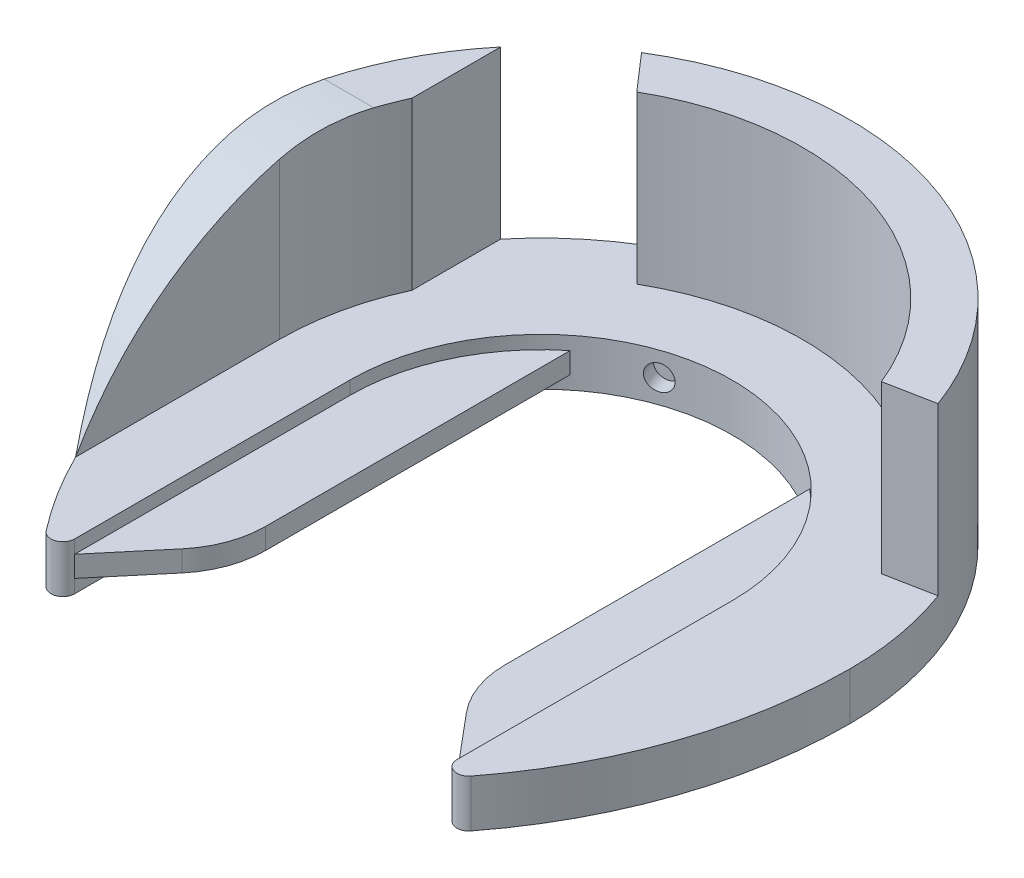
SolidWorks part; units mm, degrees
ref_plane "Front Plane" through (0, 0, 0) normal (0, 0, 1) x (1, 0, 0)
ref_plane "Top Plane" through (0, 0, 0) normal (0, 1, 0) x (1, 0, 0)
ref_plane "Right Plane" through (0, 0, 0) normal (1, 0, 0) x (0, 0, -1)
sketch "Sketch1" plane through (0, 0, 0) normal (0, 1, 0) x (1, 0, 0)
  line L3 (-40.2, 0) -> (-40.2, -57.8763)
  line L4 (40.2, 0) -> (40.2, -57.8763)
  line L5 (-25.2, -32.7206) -> (-25.2, 31.3209)
  line L6 (0, -55) -> (0, 55) construction
  line L7 (25.2, -32.7206) -> (25.2, 31.3209)
  line L8 (-40.2, -57.8763) -> (-29.8791, -45.5763)
  line L9 (40.2, -57.8763) -> (29.8791, -45.5763)
  line L10 (-55, 0) -> (-55, -42.8923)
  line L11 (55, 0) -> (55, -42.8923)
  arc A0 (65, 0) -> (-65, 0) centre (0, 0) ccw
  arc A1 (-65, 0) -> (65, 0) centre (0, 0) ccw construction
  arc A2 (40.2, 0) -> (-40.2, 0) centre (0, 0) ccw
  arc A3 (-65, 0) -> (-44.6761, -59.4076) centre (31.9875, 0) ccw
  arc A4 (65, 0) -> (44.6761, -59.4076) centre (-31.9875, 0) cw
  arc A5 (40.2, -57.8763) -> (44.6761, -59.4076) centre (42.7, -57.8763) ccw
  arc A6 (-40.2, -57.8763) -> (-44.6761, -59.4076) centre (-42.7, -57.8763) cw
  arc A8 (25.2, -32.7206) -> (29.8791, -45.5763) centre (45.2, -32.7206) ccw
  arc A9 (-25.2, -32.7206) -> (-29.8791, -45.5763) centre (-45.2, -32.7206) cw
  circle A10 centre (0, 0) radius 40.2 construction
  arc A11 (55, 0) -> (-55, 0) centre (0, 0) ccw
  point P9 (25.2, -40)
  point P19 (-25.2, -40)
  dimension "D1" = 130
  dimension "D2" = 80.4
  dimension "D4" = 2.5
  dimension "D6" = 40
  dimension "D7" = 20
  dimension "D8" = 80.4
  dimension "D9" = 110
  dimension "D3" = 50.4
  dimension "D5" = 40
extrude "Boss-Extrude1" add sketch "Sketch1" along normal blind 10 contours L11 A11 L10 A3 A6 L3 A2 L4 A5 A4 region at (-41.7941, 0, 28.9382)
extrude "Boss-Extrude2" add sketch "Sketch1<5>" along normal blind 4.4 from offset 2.8 contours A9 L5 A2 L3 L8 | L7 A8 L9 L4 A2 region at (-32.623, 0, 13.2342) region at (32.623, 0, 13.2342)
sketch "Sketch1<5>" plane through (0, 0, 0) normal (0, 1, 0) x (1, 0, 0) same geometry as "Sketch1"
extrude "Boss-Extrude3" add sketch "Sketch1<6>" along normal blind 45 contours A11 L11 A4 A0 A3 L10 region at (-60.8216, 0, 21.6377)
sketch "Sketch1<6>" plane through (0, 0, 0) normal (0, 1, 0) x (1, 0, 0) same geometry as "Sketch1"
sketch "Sketch2" plane through (0, 0, 0) normal (1, 0, 0) x (0, 0, -1)
  line L0 (-42.8923, 10) -> (-42.8923, 45)
  line L1 (-42.8923, 45) -> (17.1077, 45)
  arc A0 (-42.8923, 10) -> (17.1077, 45) centre (17.1077, -23.9286) cw
  dimension "D1" = 60
extrude "Cut-Extrude1" cut sketch "Sketch2" against normal through all both and the other way through all
sketch "Sketch3" plane through (0, 45, 0) normal (0, 1, 0) x (1, 0, 0)
  line L0 (-50.0082, 41.5232) -> (-43.344, 33.857) construction
  line L1 (-34.1593, 55.3005) -> (-27.4951, 47.6342)
  line L2 (0, 0) -> (0, 65) construction
  line L3 (0, 0) -> (-42.6438, 49.0561) construction
  line L4 (-50.0082, 41.5232) -> (-50.0082, 22.8949)
  line L7 (60.9643, 22.5468) -> (50.993, 20.6086)
  line L8 (0, 0) -> (63.8058, 12.4026) construction
  line L9 (0, 0) -> (-27.4951, 47.6342) construction
  line L10 (0, 0) -> (55, -0.0056) construction
  line L11 (60.9643, 22.5468) -> (44.8317, 31.8609) [skipped]
  line L12 (55, -0.0056) -> (55, -42.8923)
  line L13 (64.9713, 1.9326) -> (55, -0.0056) [skipped]
  arc A0 (62.7083, 17.1077) -> (-62.7083, 17.1077) centre (0, 0) ccw construction
  arc A1 (52.2717, 17.1077) -> (-52.2717, 17.1077) centre (0, 0) ccw construction
  arc A2 (55, 0) -> (-55, 0) centre (0, 0) ccw construction
  arc A3 (-50.0082, 41.5232) -> (-34.1593, 55.3005) centre (0, 0) cw
  arc A4 (-27.4951, 47.6342) -> (-43.344, 33.857) centre (0, 0) ccw
  arc A5 (-43.344, 33.857) -> (-50.0082, 22.8949) centre (0, 0) ccw
  arc A7 (55, -0.0056) -> (50.993, 20.6086) centre (0, 0) ccw
  arc A9 (50.993, 20.6086) -> (44.8317, 31.8609) centre (0, 0) ccw [skipped]
  arc A10 (60.9643, 22.5468) -> (65, 0) centre (0, 0) cw
  arc A11 (65, 0) -> (62.7083, 17.1077) centre (0, 0) ccw construction
  arc A12 (60.9643, 22.5468) -> (64.9713, 1.9326) centre (0, 0) cw [skipped]
  arc A14 (55, -42.8923) -> (65, 0) centre (-31.9875, 0) ccw construction
  arc A15 (55, -42.8923) -> (65, 0) centre (-31.9875, 0) ccw
  dimension "D4" = 2
  dimension "D1" = 21
  dimension "D2" = 41
  dimension "D3" = 10.5
  dimension "D5" = 120
extrude "Cut-Extrude2" cut sketch "Sketch3" against normal up to vertex (35 mm away) up to point (-55, 10, 0)
ref_axis "Axis1" through (0, -2.25, 0) along (0, 1, 0)
ref_plane "Plane1" through (0, 0, 0) normal (0.3256, 0, 0.9455) x (0, 1, 0)
sketch "Sketch7" plane through (0, 0, 0) normal (0.3256, 0, 0.9455) x (0, 1, 0)
  line L0 (10, -54.9243) -> (10, 10.489) construction
  circle A0 centre (5, 0) radius 2.625
  dimension "D1" = 5.25
  dimension "D2" = 5
extrude "Cut-Extrude5" cut sketch "Sketch7" against normal blind 43.5
sketch "Sketch8" plane through (0, 0, 0) normal (0, -1, 0) x (1, 0, 0)
  line L0 (40.2, 0) -> (40.2, 57.8763) construction
  line L1 (35.2, 25.5) -> (60.2, 25.5)
  line L2 (35.2, 25.5) -> (35.2, 14.5)
  line L3 (35.2, 14.5) -> (60.2, 14.5)
  line L4 (60.2, 25.5) -> (60.2, 14.5)
  point P4 (35.2, 20)
  dimension "D1" = 25
  dimension "D2" = 11
  dimension "D3" = 20
  dimension "D4" = 20
